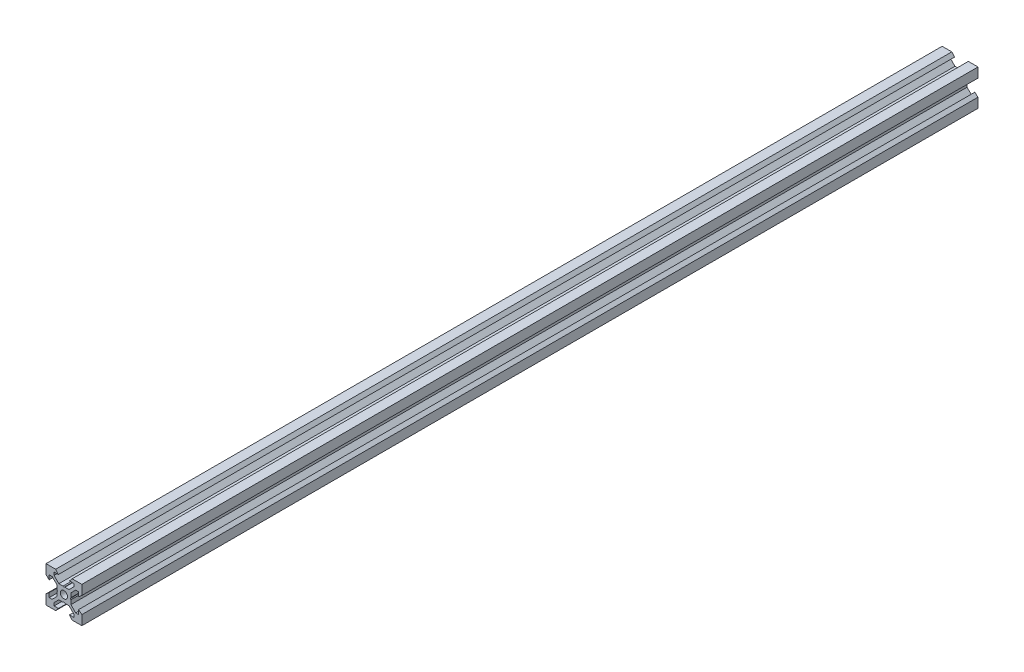
SolidWorks part; units mm, degrees
ref_plane "Front Plane" through (0, 0, 0) normal (0, 0, 1) x (1, 0, 0)
ref_plane "Top Plane" through (0, 0, 0) normal (0, 1, 0) x (1, 0, 0)
ref_plane "Right Plane" through (0, 0, 0) normal (1, 0, 0) x (0, 0, -1)
sketch "Sketch1" plane through (0, 0, 0) normal (0, 0, 1) x (1, 0, 0)
  line L0 (10, 10) -> (4.6104, 10) construction
  line L1 (10, 10) -> (10, 4.6104) construction
  line L2 (10, -10) -> (10, -4.6104) construction
  line L3 (10, -10) -> (4.6104, -10) construction
  line L4 (10, 10) -> (10, 4.6104)
  line L5 (6.5607, 5.5) -> (8.2, 5.5)
  line L6 (5.5, 8.2) -> (5.5, 6.5607)
  line L7 (10, 10) -> (4.6104, 10)
  line L8 (10, 10) -> (10, 4.6104)
  line L9 (6.5607, 5.5) -> (3.9, 2.8393)
  line L10 (5.5, 6.5607) -> (2.8393, 3.9)
  line L11 (10, 4.6104) -> (8.2, 3.1)
  line L12 (4.6104, 10) -> (3.1, 8.2)
  line L13 (8.2, 3.1) -> (8.2, 5.5)
  line L14 (3.1, 8.2) -> (5.5, 8.2)
  line L15 (-6.5607, 5.5) -> (-8.2, 5.5)
  line L16 (6.5607, -5.5) -> (8.2, -5.5)
  line L17 (3.1, -8.2) -> (5.5, -8.2)
  line L18 (8.2, -3.1) -> (8.2, -5.5)
  line L19 (4.6104, -10) -> (3.1, -8.2)
  line L20 (10, -4.6104) -> (8.2, -3.1)
  line L21 (0.5196, -3.9) -> (0, -3.6)
  line L22 (0.5196, 3.9) -> (0, 3.6)
  line L23 (3.6, 0) -> (3.9, -0.5196)
  line L24 (3.9, 0.5196) -> (3.6, 0)
  line L25 (3.9, 0.5196) -> (3.9, 2.8393)
  line L26 (2.8393, 3.9) -> (0.5196, 3.9)
  line L27 (3.9, -2.8393) -> (3.9, -0.5196)
  line L28 (2.8393, -3.9) -> (0.5196, -3.9)
  line L29 (5.5, -6.5607) -> (2.8393, -3.9)
  line L30 (6.5607, -5.5) -> (3.9, -2.8393)
  line L31 (10, -10) -> (10, -4.6104)
  line L32 (10, -10) -> (4.6104, -10)
  line L33 (5.5, -8.2) -> (5.5, -6.5607)
  line L34 (-6.5607, -5.5) -> (-8.2, -5.5)
  line L35 (10, -10) -> (10, -4.6104)
  line L36 (0, 0) -> (0, 8.2) construction
  line L37 (-10, -10) -> (-4.6104, -10) construction
  line L38 (-10, -10) -> (-10, -4.6104) construction
  line L39 (-10, 10) -> (-10, 4.6104) construction
  line L40 (-10, 10) -> (-4.6104, 10) construction
  line L41 (-10, -10) -> (-10, -4.6104)
  line L43 (-5.5, -8.2) -> (-5.5, -6.5607)
  line L44 (-10, -10) -> (-4.6104, -10)
  line L45 (-10, -10) -> (-10, -4.6104)
  line L46 (-6.5607, -5.5) -> (-3.9, -2.8393)
  line L47 (-5.5, -6.5607) -> (-2.8393, -3.9)
  line L48 (-2.8393, -3.9) -> (-0.5196, -3.9)
  line L49 (-3.9, -2.8393) -> (-3.9, -0.5196)
  line L50 (-2.8393, 3.9) -> (-0.5196, 3.9)
  line L51 (-3.9, 0.5196) -> (-3.9, 2.8393)
  line L52 (-3.9, 0.5196) -> (-3.6, 0)
  line L53 (-3.6, 0) -> (-3.9, -0.5196)
  line L54 (-0.5196, 3.9) -> (0, 3.6)
  line L55 (-0.5196, -3.9) -> (0, -3.6)
  line L56 (-10, -4.6104) -> (-8.2, -3.1)
  line L57 (-4.6104, -10) -> (-3.1, -8.2)
  line L58 (-8.2, -3.1) -> (-8.2, -5.5)
  line L59 (-3.1, -8.2) -> (-5.5, -8.2)
  line L60 (-10, -10) -> (10, -10) construction
  line L61 (-10, -10) -> (-10, 10) construction
  line L62 (-3.1, 8.2) -> (-5.5, 8.2)
  line L63 (-8.2, 3.1) -> (-8.2, 5.5)
  line L64 (-4.6104, 10) -> (-3.1, 8.2)
  line L65 (-10, 4.6104) -> (-8.2, 3.1)
  line L66 (-5.5, 6.5607) -> (-2.8393, 3.9)
  line L67 (-6.5607, 5.5) -> (-3.9, 2.8393)
  line L68 (-10, 10) -> (-10, 4.6104)
  line L69 (-10, 10) -> (-4.6104, 10)
  line L70 (-5.5, 8.2) -> (-5.5, 6.5607)
  line L71 (-10, 10) -> (10, 10) construction
  line L72 (-10, 10) -> (-10, 4.6104)
  line L73 (10, -10) -> (10, 10) construction
  line L74 (-10, -10) -> (10, 10) construction
  line L75 (-10, 10) -> (10, -10) construction
  circle A0 centre (0, 0) radius 2
  dimension "D7" = 4
  dimension "D1" = 20
  dimension "D2" = 5.3896
  dimension "D3" = 4.5
  dimension "D4" = 50
  dimension "D5" = 1.8
  dimension "D6" = 1.5104
  dimension "D8" = 5.5
  dimension "D9" = 120
  dimension "D10" = 0.3
  dimension "D11" = 2.3197
  dimension "D12" = 7.8
  dimension "D13" = 7.8
  dimension "D14" = 1.5
  dimension "D15" = 2.6607
extrude "Boss-Extrude1" add sketch "Sketch1" along normal mid plane 500 contours L70 L62 L64 L69 L68 L65 L63 L15 L67 L51 L52 L53 L49 L46 L34 L58 L56 L41 L44 L57 L59 L43 L47 L48 L55 L21 L28 L29 L33 L17 L19 L32 L31 L20 L18 L16 L30 L27 L23 L24 L25 L9 L5 L13 L11 L4 L7 L12 L14 L6 L10 region at (9.7172, 7.3052, 0)
